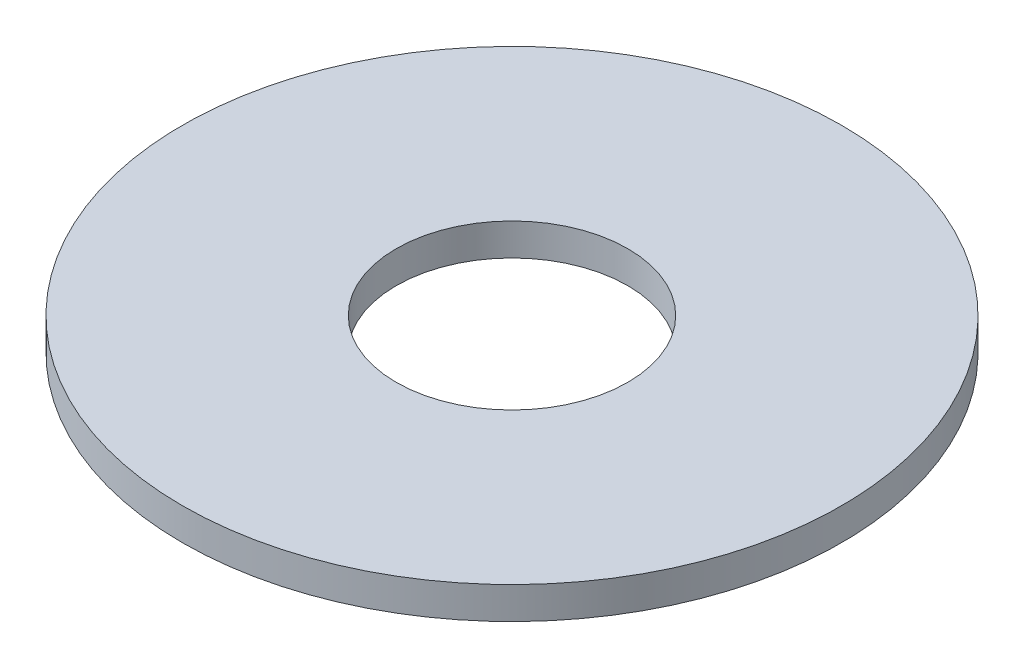
SolidWorks part; units mm, degrees
ref_plane "Front Plane" through (0, 0, 0) normal (0, 0, 1) x (1, 0, 0)
ref_plane "Top Plane" through (0, 0, 0) normal (0, 1, 0) x (1, 0, 0)
ref_plane "Right Plane" through (0, 0, 0) normal (1, 0, 0) x (0, 0, -1)
sketch "Sketch1" plane through (0, 0, 0) normal (0, 1, 0) x (1, 0, 0)
  circle A0 centre (0, 0) radius 92.5
  dimension "FLANGE_OD" = 185
extrude "Boss-Extrude1" add sketch "Sketch1" along normal blind 9
sketch "Sketch2" plane through (0, 0, 0) normal (0, 1, 0) x (1, 0, 0)
  circle A0 centre (0, 0) radius 32.5
  dimension "BORE_D" = 65
extrude "Cut-Extrude1" cut sketch "Sketch2" along normal through all
sketch "Sketch3" plane through (0, 9, 0) normal (0, 1, 0) x (1, 0, 0)
  circle A0 centre (0, 0) radius 23.4081 construction
  circle A1 centre (-23.4081, 0) radius 2.5815
  dimension "BOLT_D" = 5.1629
  dimension "BOLT_PCD" = 46.8161
extrude "Cut-Extrude2" cut sketch "Sketch3" against normal blind 6.7641 rebuild error yes
pattern_circular "CirPattern1" count 4 over 360 rebuild error yes
